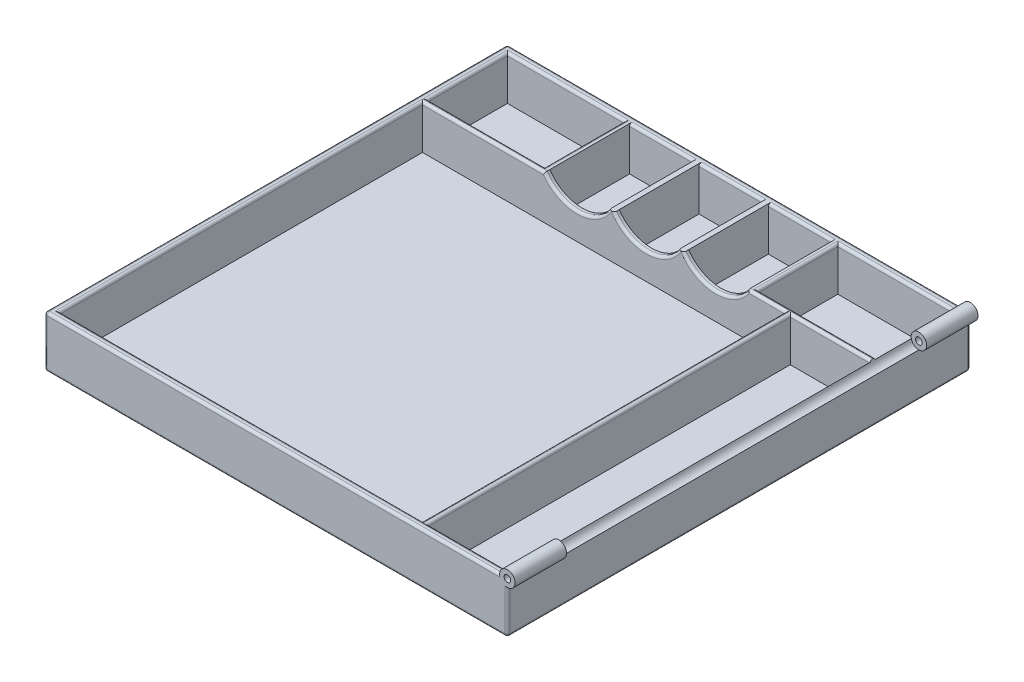
SolidWorks part; units mm, degrees
ref_plane "Front Plane" through (0, 0, 0) normal (0, 0, 1) x (1, 0, 0)
ref_plane "Top Plane" through (0, 0, 0) normal (0, 1, 0) x (1, 0, 0)
ref_plane "Right Plane" through (0, 0, 0) normal (1, 0, 0) x (0, 0, -1)
sketch "Sketch1" plane through (0, 0, 0) normal (0, 1, 0) x (1, 0, 0)
  line L5 (-114.3, -114.3) -> (114.3, -114.3)
  line L6 (-114.3, -114.3) -> (-114.3, 114.3)
  line L12 (114.3, -114.3) -> (114.3, 114.3)
  line L17 (-114.3, -114.3) -> (114.3, 114.3) construction
  line L18 (-114.3, 114.3) -> (114.3, -114.3) construction
  line L19 (-114.3, 114.3) -> (114.3, 114.3)
  point P0 (0, 0)
  dimension "D1" = 228.6
  dimension "D2" = 228.6
extrude "Boss-Extrude8" add sketch "Sketch1" along normal blind 25.4 contours L5 L12 L6 region at (0, 0, 0)
shell "Shell8" thickness 3.81 removed face at (0, 25.4, 0)
sketch "Sketch5" plane through (0, 3.81, 0) normal (0, 1, 0) x (1, 0, 0)
  line L1 (71.12, -110.49) -> (68.58, -110.49)
  line L2 (71.12, -110.49) -> (71.12, 68.58)
  line L3 (71.12, 68.58) -> (68.58, 68.58)
  line L4 (68.58, -110.49) -> (68.58, 68.58)
  line L5 (71.12, -110.49) -> (68.58, 68.58) construction
  line L6 (71.12, 68.58) -> (68.58, -110.49) construction
  line L7 (-110.49, -110.49) -> (-110.49, 110.49) construction
  line L11 (-110.49, -110.49) -> (110.49, -110.49) construction
  point P0 (69.85, -20.955)
  dimension "D1" = 2.54
  dimension "D2" = 179.07
  dimension "D3" = 179.07
extrude "Boss-Extrude12" add sketch "Sketch5" along direction (0, 1, 0) on the side of the normal up to surface (21.59 mm away) up to face at (0, 25.4, 0)
sketch "Sketch6" plane through (0, 3.81, 0) normal (0, 1, 0) x (1, 0, 0)
  line L0 (-110.49, -110.49) -> (68.58, -110.49) construction
  line L1 (110.49, 68.58) -> (-110.49, 68.58)
  line L2 (110.49, 68.58) -> (110.49, 71.12)
  line L3 (110.49, 71.12) -> (-110.49, 71.12)
  line L4 (-110.49, 68.58) -> (-110.49, 71.12)
  line L5 (110.49, 68.58) -> (-110.49, 71.12) construction
  line L6 (110.49, 71.12) -> (-110.49, 68.58) construction
  line L7 (-110.49, -110.49) -> (-110.49, 110.49) construction
  line L10 (110.49, -110.49) -> (110.49, 110.49) construction
  point P0 (0, 69.85)
  dimension "D1" = 2.54
  dimension "D2" = 179.07
extrude "Boss-Extrude13" add sketch "Sketch6" along normal up to surface (21.59 mm away) up to face at (0, 25.4, 0)
sketch "Sketch7" plane through (0, 3.81, 0) normal (0, 1, 0) x (1, 0, 0)
  line L0 (110.49, 71.12) -> (-110.49, 71.12) construction
  line L1 (-50.165, 110.49) -> (-52.705, 110.49)
  line L2 (-50.165, 110.49) -> (-50.165, 71.12)
  line L3 (-50.165, 71.12) -> (-52.705, 71.12)
  line L4 (-52.705, 110.49) -> (-52.705, 71.12)
  line L5 (-50.165, 110.49) -> (-52.705, 71.12) construction
  line L6 (-50.165, 71.12) -> (-52.705, 110.49) construction
  line L7 (-110.49, 110.49) -> (110.49, 110.49) construction
  line L8 (-110.49, 90.805) -> (110.49, 90.805) construction
  line L9 (0, 152.1028) -> (0, 71.12) construction
  line L26 (-110.49, 71.12) -> (-110.49, 110.49) construction
  line L27 (-15.875, 110.49) -> (-15.875, 71.12)
  line L28 (-18.415, 110.49) -> (-18.415, 71.12)
  line L29 (-15.875, 71.12) -> (-18.415, 71.12)
  line L30 (-15.875, 110.49) -> (-18.415, 110.49)
  line L31 (110.49, 71.12) -> (110.49, 110.49) construction
  line L32 (18.415, 110.49) -> (18.415, 71.12)
  line L33 (15.875, 110.49) -> (15.875, 71.12)
  line L34 (18.415, 71.12) -> (15.875, 71.12)
  line L35 (18.415, 110.49) -> (15.875, 110.49)
  line L36 (52.705, 110.49) -> (52.705, 71.12)
  line L37 (50.165, 110.49) -> (50.165, 71.12)
  line L38 (52.705, 71.12) -> (50.165, 71.12)
  line L39 (52.705, 110.49) -> (50.165, 110.49)
  line L40 (-52.705, 90.805) -> (52.705, 90.805) construction
  line L41 (110.49, 71.12) -> (-110.49, 71.12) construction
  point P0 (-51.435, 90.805)
  point P32 (0, 90.805)
  point P36 (0, 90.805)
  dimension "D1" = 2.54
  dimension "D2" = 4
  dimension "D3" = 31.75
extrude "Boss-Extrude14" add sketch "Sketch7" along direction (0, 1, 0) on the side of the normal up to surface (21.59 mm away) up to face at (-20.955, 25.4, 20.955)
sketch "Sketch15" plane through (0, 25.4, 0) normal (0, 1, 0) x (1, 0, 0)
  line L0 (-119.38, 68.58) -> (-20.955, 68.58) construction
  line L1 (-74.6125, -112.395) -> (-56.8325, -112.395)
  line L2 (-75.8825, -113.665) -> (-75.8825, -114.935)
  line L3 (-74.6125, -116.205) -> (-56.8325, -116.205)
  line L4 (-55.5625, -113.665) -> (-55.5625, -114.935)
  line L5 (-75.8825, -112.395) -> (-55.5625, -116.205) construction
  line L6 (-75.8825, -116.205) -> (-55.5625, -112.395) construction
  line L7 (-110.49, 68.58) -> (68.58, 68.58) construction
  line L8 (-20.955, 68.58) -> (-20.955, -110.49) construction
  line L9 (-20.955, -20.955) -> (-110.49, -20.955) construction
  line L11 (13.6525, -113.665) -> (13.6525, -114.935)
  line L12 (32.7025, -112.395) -> (14.9225, -112.395)
  line L13 (33.9725, -113.665) -> (33.9725, -114.935)
  line L14 (32.7025, -116.205) -> (14.9225, -116.205)
  line L15 (-110.49, -110.49) -> (68.58, -110.49) construction
  line L16 (-110.49, -110.49) -> (68.58, -110.49) construction
  line L17 (-110.49, -110.49) -> (-110.49, 68.58) construction
  arc A0 (-56.8325, -116.205) -> (-55.5625, -114.935) centre (-56.8325, -114.935) ccw
  arc A1 (-56.8325, -112.395) -> (-55.5625, -113.665) centre (-56.8325, -113.665) cw
  arc A2 (-74.6125, -112.395) -> (-75.8825, -113.665) centre (-74.6125, -113.665) ccw
  arc A3 (-75.8825, -114.935) -> (-74.6125, -116.205) centre (-74.6125, -114.935) ccw
  arc A4 (14.9225, -116.205) -> (13.6525, -114.935) centre (14.9225, -114.935) cw
  arc A5 (14.9225, -112.395) -> (13.6525, -113.665) centre (14.9225, -113.665) ccw
  arc A6 (32.7025, -112.395) -> (33.9725, -113.665) centre (32.7025, -113.665) cw
  arc A7 (33.9725, -114.935) -> (32.7025, -116.205) centre (32.7025, -114.935) cw
  point P0 (-65.7225, -114.3)
  point P39 (-65.7225, -20.955)
  point P40 (-20.955, -20.955)
  dimension "D1" = 1.27
  dimension "D2" = 3.81
  dimension "D3" = 3.81
  dimension "D4" = 20.32
extrude "Cut-Extrude3" [suppressed] cut sketch "Sketch15" against normal blind 17.78
ref_plane "Plane1" through (0, 0, 88.9) normal (0, 0, 1) x (1, 0, 0)
sketch "Sketch22" plane through (0, 0, -68.58) normal (0, 0, 1) x (1, 0, 0)
  line L0 (-18.415, 25.4) -> (-18.415, 3.81) construction
  line L1 (-110.49, 25.4) -> (68.58, 25.4) construction
  line L2 (-110.49, 3.81) -> (68.58, 3.81) construction
  line L3 (-50.165, 25.4) -> (-50.165, 3.81) construction
  line L4 (-15.875, 25.4) -> (-15.875, 3.81) construction
  line L5 (15.875, 25.4) -> (15.875, 3.81) construction
  line L6 (18.415, 25.4) -> (18.415, 3.81) construction
  line L12 (-50.165, 25.4) -> (-50.165, 3.81) construction
  line L18 (50.165, 25.4) -> (50.165, 3.81) construction
  line L19 (-18.415, 25.4) -> (-18.415, 3.81) construction
  line L20 (-15.875, 25.4) -> (-15.875, 3.81) construction
  line L21 (15.875, 25.4) -> (15.875, 3.81) construction
  line L22 (18.415, 25.4) -> (18.415, 3.81) construction
  line L23 (50.165, 25.4) -> (50.165, 3.81) construction
  line L25 (-50.165, 25.4) -> (-18.415, 25.4)
  line L26 (-15.875, 25.4) -> (15.875, 25.4)
  line L27 (18.415, 25.4) -> (50.165, 25.4)
  arc A3 (-50.165, 25.4) -> (-18.415, 25.4) centre (-34.29, 35.9303) ccw
  arc A4 (-15.875, 25.4) -> (15.875, 25.4) centre (0, 35.9303) ccw
  arc A5 (18.415, 25.4) -> (50.165, 25.4) centre (34.29, 35.9303) ccw
  dimension "D1" = 19.05
extrude "Cut-Extrude7" cut sketch "Sketch22" against normal up to surface (2.54 mm away) up to face at (81.5975, 14.605, -71.12)
fillet "Fillet27" radius 1.27 34 edges at (114.3, 12.7, -114.3) (0, 25.4, -114.3) (0, 0, -114.3) (0, 25.4, 114.3) (114.3, 12.7, 114.3) (0, 0, 114.3) (-114.3, 12.7, -114.3) (-114.3, 25.4, 0) (-114.3, 12.7, 114.3) (-114.3, 0, 0) (114.3, 0, 0) (34.29, 25.4, -110.49) (-34.29, 25.4, -110.49) (0, 25.4, -110.49) (90.805, 25.4, 110.49) (-81.5975, 25.4, -71.12) (-110.49, 25.4, -90.805) (-52.705, 25.4, -90.805) (-81.5975, 25.4, -110.49) (81.5975, 25.4, -71.12) (52.705, 25.4, -90.805) (110.49, 25.4, -90.805) (81.5975, 25.4, -110.49) (90.805, 25.4, -68.58) (71.12, 25.4, 20.955) (110.49, 25.4, 20.955) (68.58, 25.4, 20.955) (59.3725, 25.4, -68.58) (-20.955, 25.4, 110.49) (-110.49, 25.4, 20.955) (-80.3275, 25.4, -68.58) (34.29, 16.8803, -68.58) (-34.29, 16.8803, -68.58) (0, 16.8803, -68.58)
sketch "Sketch27" plane through (0, 0, 88.9) normal (0, 0, 1) x (1, 0, 0)
  circle A1 centre (114.3, 25.4) radius 3.81
  point P2 (0, 0)
  point P3 (0, 0)
  dimension "D1" = 7.62
extrude "Boss-Extrude17" add sketch "Sketch27" along normal blind 25.4
mirror "Mirror2" about plane through (0, 0, 0) normal (0, 0, 1) of "Boss-Extrude17"
sketch "Sketch29" plane through (0, 0, 114.3) normal (0, 0, 1) x (1, 0, 0)
  circle A0 centre (114.3, 25.4) radius 1.651
  dimension "D1" = 3.302
extrude "Cut-Extrude9" cut sketch "Sketch29" against normal up to surface (228.6 mm away) up to face at (23.1666, 15.5466, -114.3)
sketch "Sketch30" plane through (0, 25.4, 0) normal (0, 1, 0) x (1, 0, 0)
  line L0 (0, 114.3) -> (0, 0) construction
  line L3 (68.58, 0) -> (-110.49, 0) construction
  line L4 (-110.49, -110.49) -> (-110.49, 68.58) construction
  line L10 (-116.205, 66.04) -> (-116.205, 48.26)
  line L11 (-114.935, 46.99) -> (-113.665, 46.99)
  line L12 (-112.395, 48.26) -> (-112.395, 66.04)
  line L13 (-113.665, 67.31) -> (-114.935, 67.31)
  line L14 (0, 114.3) -> (0, 0) construction
  line L16 (-113.665, -67.31) -> (-114.935, -67.31)
  line L17 (-116.205, -66.04) -> (-116.205, -48.26)
  line L18 (-114.935, -46.99) -> (-113.665, -46.99)
  line L19 (-112.395, -48.26) -> (-112.395, -66.04)
  line L20 (-113.03, 114.3) -> (110.7079, 114.3) construction
  line L22 (68.58, 68.58) -> (68.58, -110.49) construction
  arc A4 (-116.205, 48.26) -> (-114.935, 46.99) centre (-114.935, 48.26) ccw
  arc A5 (-113.665, 46.99) -> (-112.395, 48.26) centre (-113.665, 48.26) ccw
  arc A6 (-112.395, 66.04) -> (-113.665, 67.31) centre (-113.665, 66.04) ccw
  arc A7 (-116.205, 66.04) -> (-114.935, 67.31) centre (-114.935, 66.04) cw
  arc A8 (-112.395, -66.04) -> (-113.665, -67.31) centre (-113.665, -66.04) cw
  arc A9 (-116.205, -66.04) -> (-114.935, -67.31) centre (-114.935, -66.04) ccw
  arc A10 (-116.205, -48.26) -> (-114.935, -46.99) centre (-114.935, -48.26) cw
  arc A11 (-113.665, -46.99) -> (-112.395, -48.26) centre (-113.665, -48.26) cw
  point P1 (-112.395, 57.15)
  point P11 (0, 57.15)
  point P12 (-114.3, 46.99)
  dimension "D4" = 1.27
  dimension "D1" = 3.81
  dimension "D5" = 20.32
  dimension "D6" = 3.81
extrude "Cut-Extrude10" [suppressed] cut sketch "Sketch30" against normal blind 5.08
sketch "Sketch31" plane through (0, 0, 0) normal (0, 0, 1) x (1, 0, 0)
  circle A0 centre (114.3, 25.4) radius 3.81
  circle A1 centre (114.3, 25.4) radius 3.81 construction
extrude "Cut-Extrude11" cut sketch "Sketch31" along normal up to surface (88.9 mm away) and the other way up to surface (88.9 mm away) up to face at (113.9413, 25.6363, 88.9) other way up to face at (113.9413, 25.6363, -88.9)
